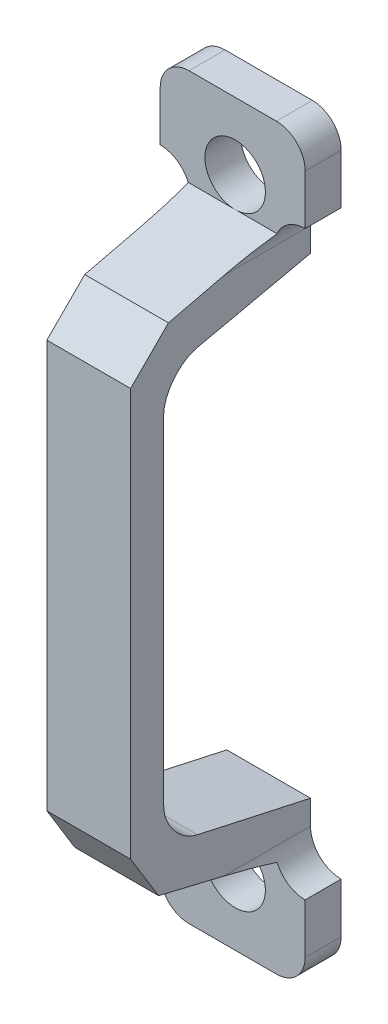
SolidWorks part; units mm, degrees
ref_plane "前视基准面" through (0, 0, 0) normal (0, 0, 1) x (1, 0, 0)
ref_plane "上视基准面" through (0, 0, 0) normal (0, 1, 0) x (1, 0, 0)
ref_plane "右视基准面" through (0, 0, 0) normal (1, 0, 0) x (0, 0, -1)
sketch "草图1" plane through (0, 0, 0) normal (0, 0, 1) x (1, 0, 0)
  line L1 (84.6239, -34.0071) -> (30.6239, -34.0071) construction
  line L2 (84.6239, -34.0071) -> (84.6239, -76.0071) construction
  line L3 (84.6239, -76.0071) -> (30.6239, -76.0071) construction
  line L7 (79.4177, -29.3519) -> (89.4859, -29.3519)
  line L8 (79.4177, -29.3519) -> (79.4177, -80.6623)
  line L9 (79.4177, -80.6623) -> (89.4859, -80.6623)
  line L10 (89.4859, -29.3519) -> (89.4859, -80.6623)
  circle A0 centre (84.6239, -34.0071) radius 2.1
  circle A3 centre (84.6239, -76.0071) radius 2.1
  point P0 (57.6239, -55.0071)
  point P9 (57.6239, -55.0071)
  dimension "D1" = 42
  dimension "D2" = 54
extrude "凸台-拉伸1" add sketch "草图1" along normal blind 2.5
sketch "草图2" plane through (89.4859, 0, 0) normal (1, 0, 0) x (0, 0, -1)
  line L0 (0, -55.0071) -> (-6.365, -55.0071) construction
  line L2 (-2.5, -80.6623) -> (-2.5, -29.3519) construction
  line L3 (11.4412, -36.0994) -> (-12.5931, -36.0994) construction
  line L4 (11.4412, -36.0994) -> (11.4412, -73.9148) construction
  line L5 (11.4412, -73.9148) -> (-12.5931, -73.9148) construction
  line L6 (-12.5931, -36.0994) -> (-12.5931, -73.9148) construction
  line L7 (11.4412, -36.0994) -> (-12.5931, -73.9148) construction
  line L8 (11.4412, -73.9148) -> (-12.5931, -36.0994) construction
  line L9 (-22.8373, -38.497) -> (-12.5, -38.497) construction
  line L10 (-22.8373, -38.497) -> (-22.8373, -71.5172) construction
  line L11 (-22.8373, -71.5172) -> (-12.5, -71.5172) construction
  line L12 (-12.5, -38.497) -> (-12.5, -71.5172) construction
  line L13 (-22.8373, -38.497) -> (-12.5, -71.5172) construction
  line L14 (-22.8373, -71.5172) -> (-12.5, -38.497) construction
  line L15 (-12.5, -71.5172) -> (-2.5, -73.9148)
  line L16 (-2.5, -73.9148) -> (-2.5, -36.0994)
  line L17 (-2.5, -36.0994) -> (-12.5, -38.497)
  line L18 (-12.5, -38.497) -> (-12.5, -71.5172)
  point P1 (-0.5759, -55.0071)
  point P7 (-17.6686, -55.0071)
  point P14 (-2.5, -73.9148)
  point P17 (-14.5, -71.5172)
  dimension "D1" = 10
extrude "凸台-拉伸2" add sketch "草图2" against normal up to surface (10.0682 mm away) up to face at (79.4177, -55.0071, 1.25)
sketch "草图3" plane through (89.4859, 0, 0) normal (1, 0, 0) x (0, 0, -1)
  line L0 (-14.5, -55.0071) -> (-17.2067, -55.0071) construction
  line L2 (0, -80.6623) -> (0, -29.3519) construction
  line L3 (-5.0776, -71.3953) -> (0, -71.3953) construction
  line L4 (-5.0776, -71.3953) -> (-5.0776, -38.6189) construction
  line L5 (-5.0776, -38.6189) -> (0, -38.6189) construction
  line L6 (0, -71.3953) -> (0, -38.6189) construction
  line L7 (-5.0776, -71.3953) -> (0, -38.6189) construction
  line L8 (-5.0776, -38.6189) -> (0, -71.3953) construction
  line L9 (-10.1988, -69.151) -> (0, -71.3953)
  line L10 (-13.2647, -40.8632) -> (-10.1988, -40.8632) construction
  line L11 (-13.2647, -40.8632) -> (-13.2647, -69.151) construction
  line L12 (-13.2647, -69.151) -> (-10.1988, -69.151) construction
  line L13 (-10.1988, -40.8632) -> (-10.1988, -69.151) construction
  line L14 (-13.2647, -40.8632) -> (-10.1988, -69.151) construction
  line L15 (-13.2647, -69.151) -> (-10.1988, -40.8632) construction
  line L16 (0, -71.3953) -> (0, -38.6189)
  line L17 (0, -38.6189) -> (-10.1988, -40.8632)
  line L18 (-10.1988, -40.8632) -> (-10.1988, -69.151)
  point P1 (-2.5388, -55.0071)
  point P9 (-11.7318, -55.0071)
  point P14 (-12.307, -42.4942)
  point P15 (-10.1988, -40.8632)
  point P16 (0, -38.6189)
extrude "切除-拉伸1" cut sketch "草图3" against normal through all both and the other way through all
sketch "草图4" plane through (0, 0, 12.5) normal (0, 0, 1) x (1, 0, 0)
  line L0 (84.4518, -40.8866) -> (84.4518, -50.8041) construction
  line L2 (79.4177, -55.0071) -> (74.8166, -55.0071) construction
  line L4 (79.4177, -36.9415) -> (79.4177, -73.0727) construction
  line L5 (79.4177, -71.5172) -> (79.4177, -38.497) construction
  line L6 (79.4177, -73.9148) -> (79.4177, -80.6623) construction
  line L7 (81.5444, -36.9415) -> (81.5444, -73.0727)
  line L8 (77.291, -36.9415) -> (77.291, -73.0727)
  line L9 (89.4859, -36.9415) -> (89.4859, -73.0727) construction
  line L10 (87.3592, -36.9415) -> (87.3592, -73.0727)
  line L11 (91.6126, -36.9415) -> (91.6126, -73.0727)
  arc A0 (81.5444, -36.9415) -> (77.291, -36.9415) centre (79.4177, -36.9415) ccw
  arc A1 (77.291, -73.0727) -> (81.5444, -73.0727) centre (79.4177, -73.0727) ccw
  arc A2 (87.3592, -36.9415) -> (91.6126, -36.9415) centre (89.4859, -36.9415) cw
  arc A3 (91.6126, -73.0727) -> (87.3592, -73.0727) centre (89.4859, -73.0727) cw
  point P10 (79.4177, -55.0071)
  point P17 (89.4859, -55.0071)
extrude "切除-拉伸2" cut sketch "草图4" against normal through all both and the other way through all
fillet "圆角1" radius 3 2 edges at (84.4518, -40.8632, 10.1988) (84.4518, -69.151, 10.1988)
fillet "圆角2" radius 2 4 edges at (89.4859, -80.6623, 1.25) (79.4177, -80.6623, 1.25) (79.4177, -29.3519, 1.25) (89.4859, -29.3519, 1.25)
chamfer "倒角2" distance 2 angle 45 2 edges at (84.4518, -38.497, 12.5) (84.4518, -71.5172, 12.5)
